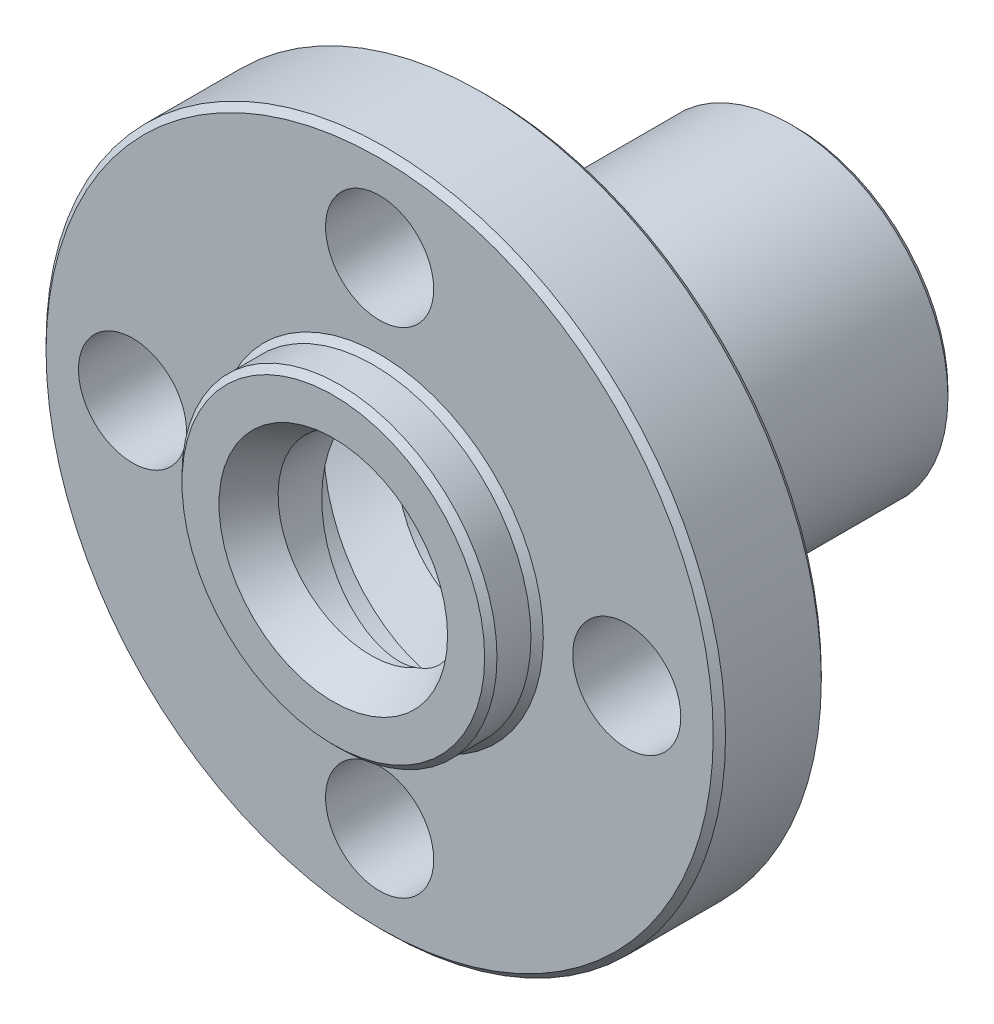
SolidWorks part; units mm, degrees
ref_plane "Plan de face" through (0, 0, 0) normal (0, 0, 1) x (1, 0, 0)
ref_plane "Plan de dessus" through (0, 0, 0) normal (0, 1, 0) x (1, 0, 0)
ref_plane "Plan de droite" through (0, 0, 0) normal (1, 0, 0) x (0, 0, -1)
sketch "Esquisse1" plane through (0, 0, 0) normal (0, 0, 1) x (1, 0, 0)
  circle A0 centre (0, 0) radius 8 construction
  circle A1 centre (0, 0) radius 5.1
  circle A2 centre (0, 0) radius 11
  circle A3 centre (0, 8) radius 1.75
  circle A4 centre (0, 0) radius 8 construction
  circle A5 centre (8, 0) radius 1.75
  circle A6 centre (0, 0) radius 8 construction
  circle A7 centre (0, -8) radius 1.75
  circle A8 centre (0, 0) radius 8 construction
  circle A9 centre (-8, 0) radius 1.75
  point P19 (0, 0)
  dimension "D1" = 22
  dimension "D2" = 16
  dimension "D3" = 10.2
  dimension "D4" = 3.5
  dimension "D5" = 4
extrude "Boss.-Extru.1" add sketch "Esquisse1" along normal blind 3.5
sketch "Esquisse2" plane through (0, 0, 3.5) normal (0, 0, 1) x (1, 0, 0)
  circle A0 centre (0, 0) radius 5.1 construction
  circle A1 centre (0, 0) radius 5.1
  circle A2 centre (0, 0) radius 3
  dimension "D1" = 6
extrude "Boss.-Extru.2" add sketch "Esquisse2" along normal blind 1.5 and the other way blind 13.5
chamfer "Chanfrein2" distance 0.7 angle 60 2 edges at (3, 0, 5) (3, 0, -10) first distance on face at (5.1, 0, 5) first distance on face at (3, 0, -10)
sketch "Esquisse5" plane through (0, 0, 3.5) normal (0, 0, 1) x (1, 0, 0)
  circle A0 centre (0, 0) radius 3.7 construction
  circle A1 centre (0, 0) radius 3.7
curve "Hélice/Spirale1" pitch 4.5 height 25 turns 5.5556
sketch "Esquisse6" plane through (0, 0, 0) normal (1, 0, 0) x (0, 0, -1)
  line L0 (9.367, 4.5) -> (8.7037, 4.5)
  line L1 (8.7037, 4.5) -> (7.4092, 2.2579)
  line L2 (7.4092, 2.2579) -> (10.6615, 2.2579)
  line L3 (9.0353, 4.5) -> (9.0353, 2.2579) construction
  line L4 (9.367, 4.5) -> (10.6615, 2.2579)
  line L5 (10, 5.1) -> (0, 5.1) construction
  dimension "D1" = 60
  dimension "D2" = 0.6
sweep "Enlèvement de matière-Balayage1" cut profiles "Esquisse6" path "Hélice/Spirale1"
chamfer "Chanfrein3" distance 0.2 angle 45 6 edges at (5.1, 0, -10) (11, 0, 0) (5.1, 0, 3.5) (5.1, 0, 5) (11, 0, 3.5) (5.1, 0, 0)
